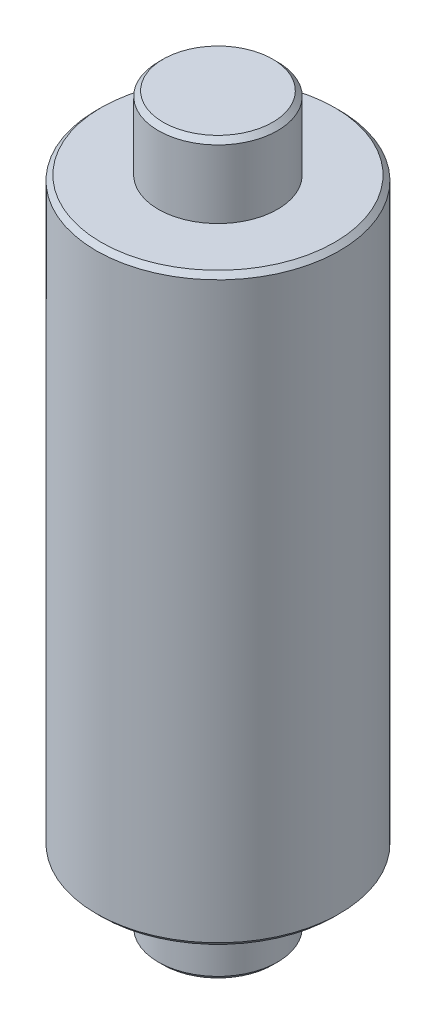
SolidWorks part; units mm, degrees
ref_plane "Front Plane" through (0, 0, 0) normal (0, 0, 1) x (1, 0, 0)
ref_plane "Top Plane" through (0, 0, 0) normal (0, 1, 0) x (1, 0, 0)
ref_plane "Right Plane" through (0, 0, 0) normal (1, 0, 0) x (0, 0, -1)
sketch "Sketch1" plane through (0, 0, 0) normal (0, 1, 0) x (1, 0, 0)
  circle A0 centre (0, 0) radius 2.45
  dimension "D1" = 4.9
extrude "Boss-Extrude1" add sketch "Sketch1" along normal blind 30
chamfer "Chamfer1" distance 0.2 angle 45 2 edges at (0, 30, 2.45) (0, 0, 2.45)
ref_plane "Plane1" through (0, 15, 0) normal (0, 1, 0) x (1, 0, 0)
sketch "Sketch2" plane through (0, 15, 0) normal (0, 1, 0) x (1, 0, 0)
  circle A0 centre (0, 0) radius 5
  dimension "D1" = 10
extrude "Boss-Extrude2" add sketch "Sketch2" along normal mid plane 24
chamfer "Chamfer2" distance 0.2 angle 45 2 edges at (0, 3, 5) (0, 27, 5)
